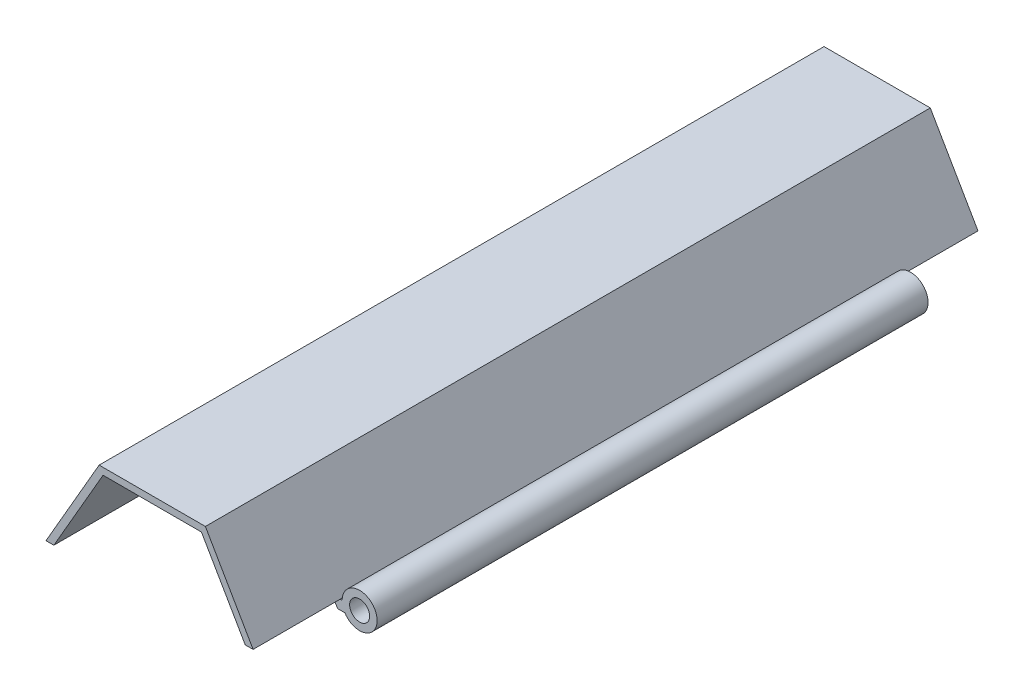
SolidWorks part; units mm, degrees
ref_plane "Front Plane" through (0, 0, 0) normal (0, 0, 1) x (1, 0, 0)
ref_plane "Top Plane" through (0, 0, 0) normal (0, 1, 0) x (1, 0, 0)
ref_plane "Right Plane" through (0, 0, 0) normal (1, 0, 0) x (0, 0, -1)
sketch "Sketch1" plane through (0, 0, 0) normal (0, 0, 1) x (1, 0, 0)
  line L0 (-27, 0) -> (-25, 0)
  line L1 (25, 0) -> (12.5, 21.6506)
  line L2 (12.5, 21.6506) -> (-12.5, 21.6506)
  line L3 (-12.5, 21.6506) -> (-25, 0)
  line L7 (25.6259, 2.38) -> (13.5, 23.3827)
  line L8 (13.5, 23.3827) -> (-13.5, 23.3827)
  line L9 (-13.5, 23.3827) -> (-27, 0)
  line L13 (25, 0) -> (27, 0)
  line L14 (25, 0) -> (25, 2.38)
  line L15 (13.5, -23.3827) -> (20.25, -11.6913) [skipped]
  line L16 (12.5, -21.6506) -> (14.3341, -18.4738) [skipped]
  line L17 (-13.5, -23.3827) -> (0, -23.3827) [skipped]
  line L18 (-12.5, -21.6506) -> (-8.8318, -21.6506) [skipped]
  line L19 (-27, 0) -> (-20.25, -11.6913) [skipped]
  line L20 (-25, 0) -> (-23.1659, -3.1768) [skipped]
  line L22 (25.6259, 2.38) -> (26.1509, 2.38)
  line L23 (27, 0) -> (26.8418, 0)
  arc A0 (18.75, 10.8253) -> (-18.75, 10.8253) centre (0, 0) ccw construction
  arc A1 (23.1659, 3.1768) -> (-23.1659, 3.1768) centre (0, 0) ccw construction
  circle A2 centre (30.5959, 2.38) radius 2.54
  arc A3 (26.8418, 0) -> (26.1509, 2.38) centre (30.5959, 2.38) ccw
  dimension "D5" = 5.08
  dimension "D6" = 8.89
  dimension "D1" = 50
  dimension "D2" = 2
  dimension "D3" = 2.38
  dimension "D4" = 4.97
extrude "Boss-Extrude1" add sketch "Sketch1" along normal blind 184.2 contours L23 A3 L22 L7 L8 L9 L0 L3 L2 L1 L13 A2 region at (-19.6693, 11.3561, 0)
sketch "Sketch5" plane through (0, 0, 184.2) normal (0, 0, 1) x (1, 0, 0)
  line L0 (23.6259, 2.38) -> (26.1509, 2.38)
  line L1 (25, 0) -> (12.5, 21.6506) construction
  line L2 (25.6259, 2.38) -> (26.1509, 2.38) construction
  line L4 (23.6259, 2.38) -> (25, 0)
  line L5 (25, 0) -> (26.8418, 0)
  arc A0 (26.8418, 0) -> (26.1509, 2.38) centre (30.5959, 2.38) ccw construction
  arc A1 (26.8418, 0) -> (26.1509, 2.38) centre (30.5959, 2.38) ccw
  circle A2 centre (30.5959, 2.38) radius 2.54 construction
extrude "Cut-Extrude4" cut sketch "Sketch5" against normal blind 22.098
sketch "Sketch6" plane through (0, 0, 0) normal (0, 0, -1) x (-1, 0, 0)
  line L0 (-23.6259, 2.38) -> (-26.1509, 2.38)
  line L1 (-25, 0) -> (-12.5, 21.6506) construction
  line L3 (-23.6259, 2.38) -> (-25, 0)
  line L4 (-25, 0) -> (-26.8418, 0)
  arc A0 (-26.1509, 2.38) -> (-26.8418, 0) centre (-30.5959, 2.38) ccw
extrude "Cut-Extrude5" cut sketch "Sketch6" against normal blind 22.098
